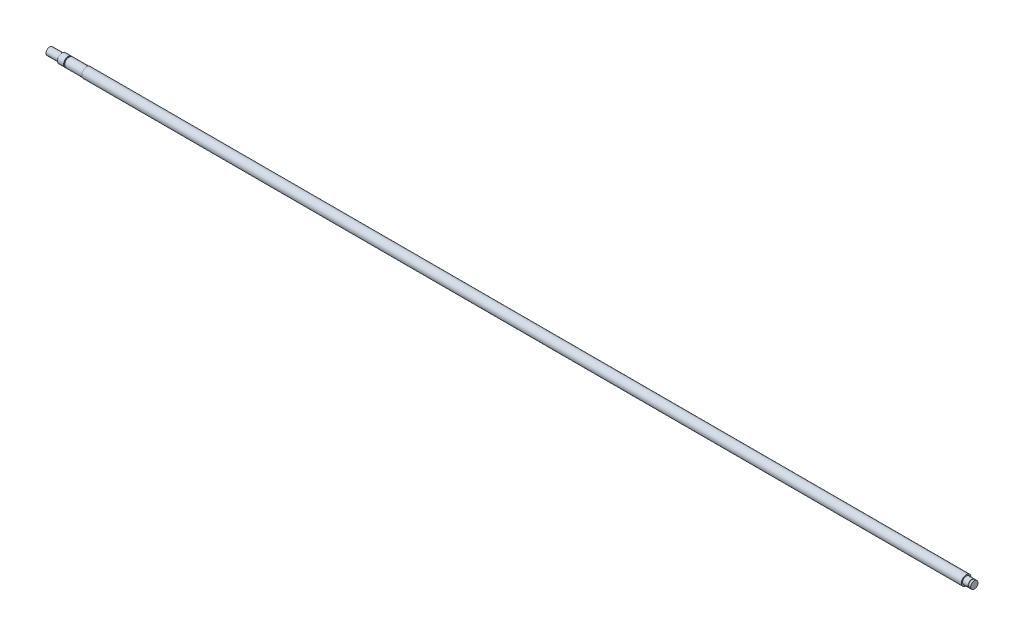
SolidWorks part; units mm, degrees
material "Plain Carbon Steel"
ref_plane "Front Plane" through (0, 0, 0) normal (0, 0, 1) x (1, 0, 0)
ref_plane "Top Plane" through (0, 0, 0) normal (0, 1, 0) x (1, 0, 0)
ref_plane "Right Plane" through (0, 0, 0) normal (1, 0, 0) x (0, 0, -1)
sketch "Sketch1" plane through (0, 0, 0) normal (0, 0, 1) x (1, 0, 0)
  line L0 (-60, 0) -> (1440, 0)
  line L1 (1440, 0) -> (1440, 6)
  line L2 (1440, 6) -> (1437.15, 6)
  line L3 (1437.15, 6) -> (1437.15, 5.65)
  line L4 (1437.15, 5.65) -> (1436, 5.65)
  line L5 (1436, 5.65) -> (1436, 6)
  line L6 (1436, 6) -> (1427, 6)
  line L7 (1427, 6) -> (1427, 8)
  line L8 (1427, 8) -> (0, 8)
  line L9 (0, 8) -> (0, 7.5)
  line L10 (0, 7.5) -> (-28, 7.5)
  line L11 (-28, 7.5) -> (-28, 6)
  line L12 (-28, 6) -> (-30, 6)
  line L13 (-30, 6) -> (-30, 7.5)
  line L14 (-30, 7.5) -> (-40, 7.5)
  line L15 (-40, 7.5) -> (-40, 6)
  line L16 (-40, 6) -> (-60, 6)
  line L17 (-60, 6) -> (-60, 0)
  point P18 (713.5, 8)
  dimension "D1" = 2
  dimension "D2" = 20
  dimension "D3" = 12
  dimension "D4" = 40
  dimension "D5" = 1.15
  dimension "D6" = 0.35
  dimension "D7" = 9
  dimension "D8" = 13
  dimension "D9" = 1500
  dimension "D10" = 6
  dimension "D11" = 7.5
  dimension "D12" = 8
revolve "Revolve1" add sketch "Sketch1" angle 360 about L0
